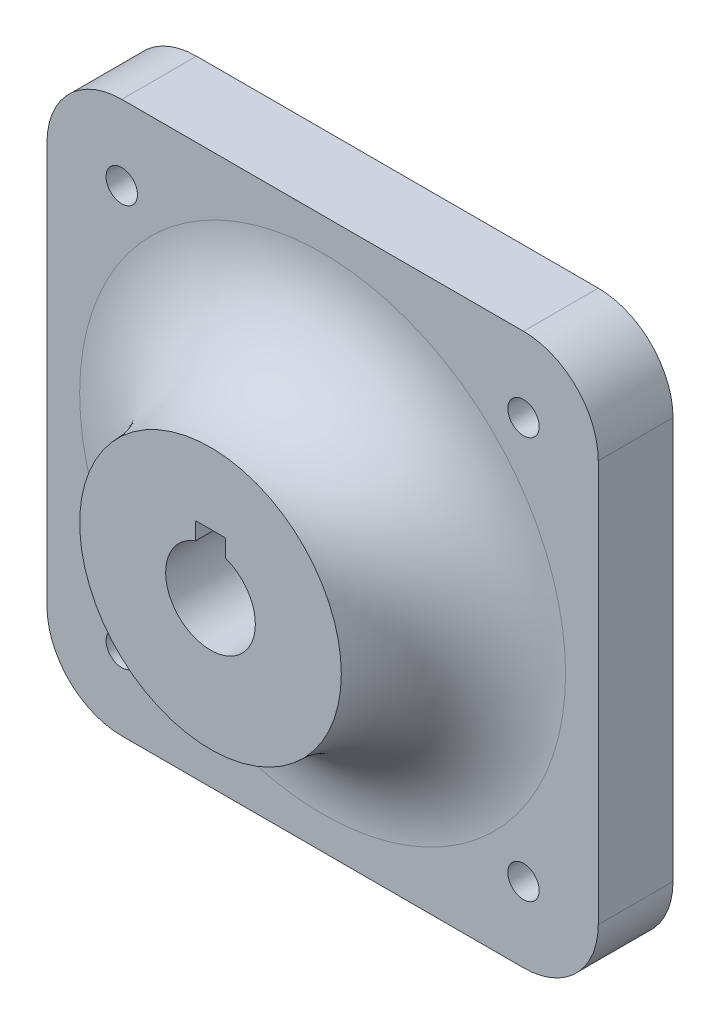
SolidWorks part; units mm, degrees
ref_plane "Front Plane" through (0, 0, 0) normal (0, 0, 1) x (1, 0, 0)
ref_plane "Top Plane" through (0, 0, 0) normal (0, 1, 0) x (1, 0, 0)
ref_plane "Right Plane" through (0, 0, 0) normal (1, 0, 0) x (0, 0, -1)
sketch "Spacing" plane through (0, 0, 0) normal (0, 0, 1) x (1, 0, 0)
  line L1 (-26.8701, -26.8701) -> (26.8701, -26.8701)
  line L2 (-26.8701, -26.8701) -> (-26.8701, 26.8701)
  line L3 (-26.8701, 26.8701) -> (26.8701, 26.8701)
  line L4 (26.8701, -26.8701) -> (26.8701, 26.8701)
  line L5 (-26.8701, -26.8701) -> (26.8701, 26.8701) construction
  line L6 (-26.8701, 26.8701) -> (26.8701, -26.8701) construction
  point P0 (0, 0)
  dimension "D1" = 76
sketch "Sketch1" plane through (0, 0, 7) normal (0, 0, 1) x (1, 0, 0)
  line L0 (36.8701, -26.8701) -> (36.8701, 26.8701)
  line L1 (26.8701, 36.8701) -> (-26.8701, 36.8701)
  line L2 (-36.8701, 26.8701) -> (-36.8701, -26.8701)
  line L3 (26.8701, -36.8701) -> (-26.8701, -36.8701)
  arc A0 (26.8701, -36.8701) -> (36.8701, -26.8701) centre (26.8701, -26.8701) ccw
  arc A1 (-36.8701, -26.8701) -> (-26.8701, -36.8701) centre (-26.8701, -26.8701) ccw
  arc A2 (-26.8701, 36.8701) -> (-36.8701, 26.8701) centre (-26.8701, 26.8701) ccw
  arc A3 (36.8701, 26.8701) -> (26.8701, 36.8701) centre (26.8701, 26.8701) ccw
  circle A6 centre (26.8701, -26.8701) radius 2.1
  circle A7 centre (-26.8701, -26.8701) radius 2.1
  circle A8 centre (-26.8701, 26.8701) radius 2.1
  circle A9 centre (26.8701, 26.8701) radius 2.1
  dimension "D1" = 20
  dimension "D2" = 4.2
extrude "Boss-Extrude1" add sketch "Sketch1" along normal blind 10 from offset 2
sketch "Sketch7" plane through (0, 0, 9) normal (0, 0, -1) x (-1, 0, 0)
  circle A0 centre (26.8701, -26.8701) radius 2.1 construction
  circle A1 centre (26.8701, -26.8701) radius 2.1
  circle A2 centre (26.8701, -26.8701) radius 3.6
  circle A3 centre (-26.8701, -26.8701) radius 3.6
  circle A4 centre (-26.8701, -26.8701) radius 2.1
  circle A5 centre (-26.8701, 26.8701) radius 3.6
  circle A6 centre (-26.8701, 26.8701) radius 2.1
  circle A7 centre (26.8701, 26.8701) radius 3.6
  circle A8 centre (26.8701, 26.8701) radius 2.1
  point P4 (14.9615, -15.803)
  point P6 (-19.3685, 23.6651)
  point P15 (-26.8701, 26.8701)
  point P17 (26.8701, 26.8701)
  dimension "D1" = 7.2
  dimension "D2" = 2
  dimension "D3" = 2
extrude "Boss-Extrude3" add sketch "Sketch7" along normal up to surface (2 mm away)
sketch "Sketch3" plane through (0, 0, 19) normal (0, 0, 1) x (1, 0, 0)
  circle A0 centre (0, 0) radius 17.5
  dimension "D1" = 35
extrude "Boss-Extrude2" add sketch "Sketch3" along normal blind 15
sketch "Sketch2" plane through (0, 0, 9) normal (0, 0, -1) x (-1, 0, 0)
  circle A0 centre (0, 0) radius 15
  dimension "D1" = 30
extrude "Cut-Extrude1" cut sketch "Sketch2" against normal blind 15
fillet "Fillet1" radius 15 1 edges at (17.5, 0, 19)
sketch "Sketch4" plane through (0, 0, 34) normal (0, 0, 1) x (1, 0, 0)
  circle A0 centre (0, 0) radius 6
  dimension "D1" = 12
extrude "Cut-Extrude2" cut sketch "Sketch4" against normal through all
sketch "Sketch5" plane through (0, 0, 34) normal (0, 0, 1) x (1, 0, 0)
  line L1 (2, 8) -> (-2, 8)
  line L2 (2, 8) -> (2, 5.6569)
  line L3 (2, 5.6569) -> (-2, 5.6569)
  line L4 (-2, 8) -> (-2, 5.6569)
  line L5 (2, 8) -> (-2, 5.6569) construction
  line L6 (2, 5.6569) -> (-2, 8) construction
  circle A0 centre (0, 0) radius 6 construction
  point P0 (0, 6.8284)
  dimension "D1" = 4
  dimension "D2" = 2
extrude "Cut-Extrude3" cut sketch "Sketch5" against normal through all
